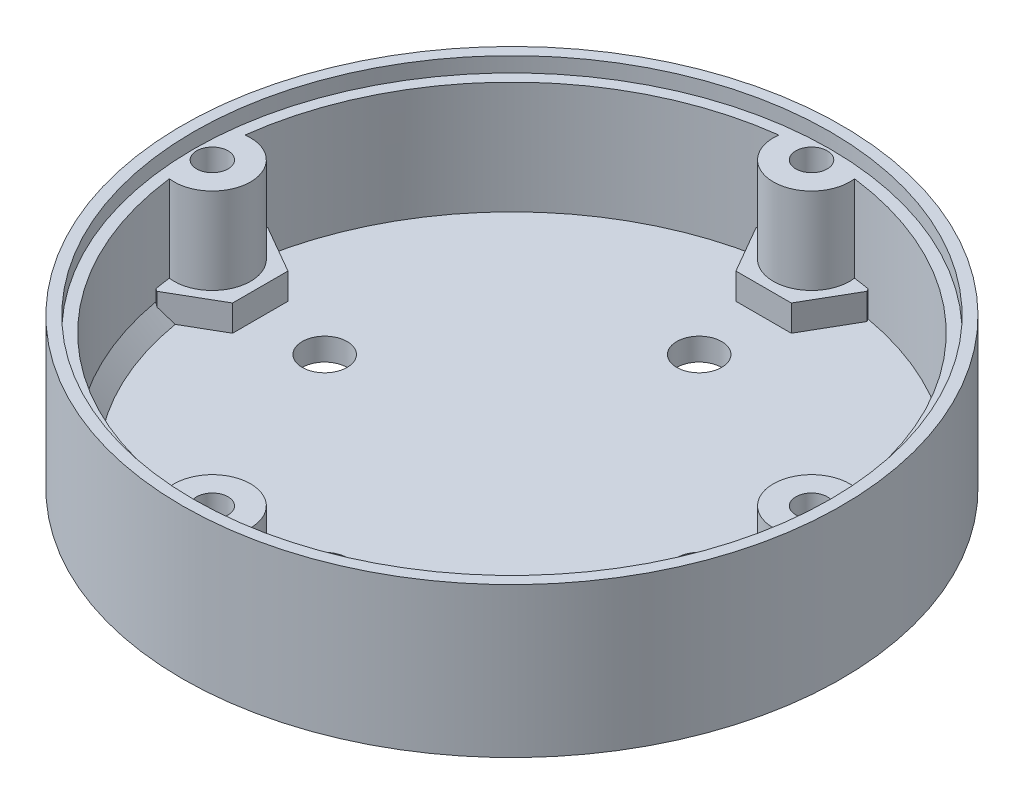
SolidWorks part; units mm, degrees
ref_plane "Alzado" through (0, 0, 0) normal (0, 0, 1) x (1, 0, 0)
ref_plane "Planta" through (0, 0, 0) normal (0, 1, 0) x (1, 0, 0)
ref_plane "Vista lateral" through (0, 0, 0) normal (1, 0, 0) x (0, 0, -1)
sketch "Croquis1" plane through (0, 0, 0) normal (0, 1, 0) x (1, 0, 0)
  circle A0 centre (0, 0) radius 44
  dimension "D1" = 88
extrude "Saliente-Extruir1" add sketch "Croquis1" along normal blind 20
sketch "Croquis3" plane through (0, 20, -20) normal (0, -1, 0) x (1, 0, 0)
  line L0 (0, 20) -> (50000, 20) construction
  line L1 (0, 0) -> (0, 50000) construction
  circle A0 centre (-40, 20) radius 2.1
  circle A2 centre (0, 60) radius 2.1
  circle A3 centre (40, 20) radius 2.1
  circle A4 centre (0, -20) radius 2.1
  point P7 (0, 0)
  point P18 (0, 20)
  dimension "D1" = 4.2
  dimension "D2" = 40
  dimension "D3" = 4
extrude "Cortar-Extruir3" cut sketch "Croquis3" along normal through all
sketch "Croquis5" plane through (0, 0, 0) normal (0, -1, 0) x (1, 0, 0)
  line L0 (40, -3.926) -> (43.4, -1.963)
  line L1 (3.926, 40) -> (1.963, 43.4)
  line L2 (1.963, 43.4) -> (-1.963, 43.4)
  line L3 (-1.963, 43.4) -> (-3.926, 40)
  line L4 (-3.926, 40) -> (-1.963, 36.6)
  line L5 (-1.963, 36.6) -> (1.963, 36.6)
  line L6 (1.963, 36.6) -> (3.926, 40)
  line L7 (43.4, -1.963) -> (43.4, 1.963)
  line L8 (43.4, 1.963) -> (40, 3.926)
  line L9 (40, 3.926) -> (36.6, 1.963)
  line L10 (36.6, 1.963) -> (36.6, -1.963)
  line L11 (36.6, -1.963) -> (40, -3.926)
  line L12 (-3.926, -40) -> (-1.963, -43.4)
  line L13 (-1.963, -43.4) -> (1.963, -43.4)
  line L14 (1.963, -43.4) -> (3.926, -40)
  line L15 (3.926, -40) -> (1.963, -36.6)
  line L16 (1.963, -36.6) -> (-1.963, -36.6)
  line L17 (-1.963, -36.6) -> (-3.926, -40)
  line L18 (-40, 3.926) -> (-43.4, 1.963)
  line L19 (-43.4, 1.963) -> (-43.4, -1.963)
  line L20 (-43.4, -1.963) -> (-40, -3.926)
  line L21 (-40, -3.926) -> (-36.6, -1.963)
  line L22 (-36.6, -1.963) -> (-36.6, 1.963)
  line L23 (-36.6, 1.963) -> (-40, 3.926)
  circle A0 centre (0, 40) radius 3.4 construction
  circle A1 centre (40, 0) radius 3.4 construction
  circle A2 centre (0, -40) radius 3.4 construction
  circle A3 centre (-40, 0) radius 3.4 construction
  point P36 (0, 0)
  dimension "D1" = 6.8
  dimension "D2" = 4
extrude "Cortar-Extruir5" cut sketch "Croquis5" against normal blind 3.5
shell "Vaciado1" thickness 3 removed face at (-40, 20, -2.1)
sketch "Croquis2" plane through (0, 0, 0) normal (0, -1, 0) x (1, 0, 0)
  line L0 (0, 0) -> (0, 50000) construction
  line L1 (0, 0) -> (50000, 0) construction
  circle A0 centre (0, 25) radius 3
  circle A1 centre (25, 0) radius 3
  circle A2 centre (0, -25) radius 3
  circle A3 centre (-25, 0) radius 3
  point P16 (0, 0)
  dimension "D1" = 6
  dimension "D2" = 50
  dimension "D3" = 4
extrude "Cortar-Extruir1" cut sketch "Croquis2" against normal through all
sketch "Croquis4" plane through (0, 20, 0) normal (0, 1, 0) x (1, 0, 0)
  circle A0 centre (0, 0) radius 42.5
  dimension "D1" = 85
extrude "Cortar-Extruir4" cut sketch "Croquis4" against normal blind 2
chamfer "Chaflán1" distance 2 angle 45 1 edges at (-28.9914, 3, 28.9914)
